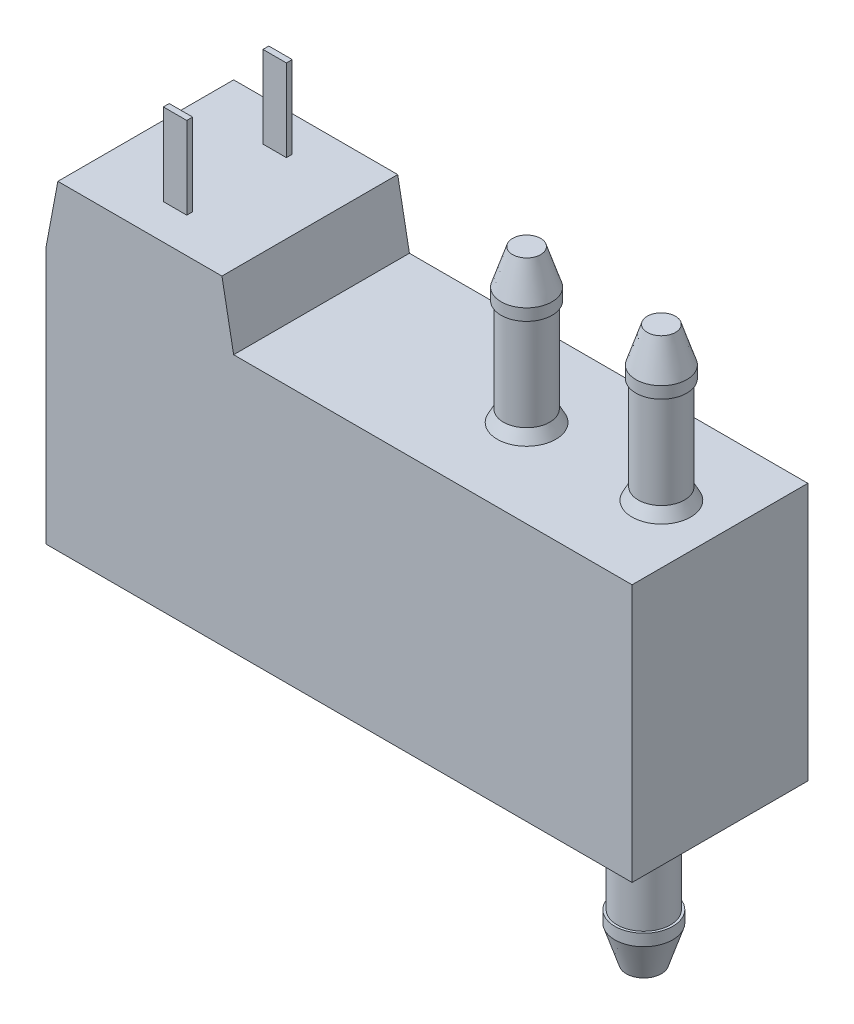
SolidWorks part; units mm, degrees
ref_plane "Front Plane" through (0, 0, 0) normal (0, 0, 1) x (1, 0, 0)
ref_plane "Top Plane" through (0, 0, 0) normal (0, 1, 0) x (1, 0, 0)
ref_plane "Right Plane" through (0, 0, 0) normal (1, 0, 0) x (0, 0, -1)
sketch "Sketch1" plane through (0, 0, 0) normal (0, 0, 1) x (1, 0, 0)
  line L1 (-25, -11) -> (25, -11)
  line L2 (-25, -11) -> (-25, 11)
  line L3 (-25, 11) -> (25, 11)
  line L4 (25, -11) -> (25, 11)
  line L5 (-25, -11) -> (25, 11) construction
  line L6 (-25, 11) -> (25, -11) construction
  point P0 (0, 0)
  dimension "D1" = 22
  dimension "D2" = 50
extrude "Boss-Extrude1" add sketch "Sketch1" along normal mid plane 15
sketch "Sketch3" plane through (0, 0, 0) normal (0, 0, 1) x (1, 0, 0)
  line L0 (-25, 11) -> (-24, 16.316)
  line L1 (-24, 16.316) -> (-10, 16.316)
  line L2 (-10, 16.316) -> (-9, 11)
  line L3 (25, 11) -> (-25, 11) construction
  line L4 (-9, 11) -> (-25, 11)
  point P4 (-17, 16.316)
  point P8 (-17, 11)
  dimension "D1" = 16
  dimension "D2" = 14
extrude "Boss-Extrude3" add sketch "Sketch3" along normal up to surface and the other way up to surface up to face at (0, 0, 7.5) other way up to face at (0, 0, -7.5)
sketch "Sketch4" plane through (0, 11, 0) normal (0, 1, 0) x (1, 0, 0)
  line L0 (25, 0) -> (-9, 0) construction
  line L1 (25, -7.5) -> (25, 7.5) construction
  line L2 (-9, -7.5) -> (-9, 7.5) construction
  point P6 (8.5, 0)
  point P7 (20, 0)
  dimension "D1" = 16.5
  dimension "D2" = 5
ref_axis "Axis1" through (8.5, 11, 0) along (0, 1, 0)
ref_axis "Axis2" through (20, 11, 0) along (0, 1, 0)
sketch "Sketch5" plane through (0, 0, 0) normal (0, 0, 1) x (1, 0, 0)
  line L0 (8.5, 11) -> (11, 11)
  line L1 (25, 11) -> (-9, 11) construction
  line L2 (11, 11) -> (10.4748, 12)
  line L3 (10.4748, 12) -> (10.4748, 20)
  line L4 (10.4748, 20) -> (10.6748, 20)
  line L5 (10.6748, 20) -> (10.6748, 21)
  line L6 (10.6748, 21) -> (9.7, 24)
  line L7 (9.7, 24) -> (8.5, 24)
  line L8 (8.5, 11) -> (8.5, 23.2634) construction
  line L9 (8.5, 24) -> (8.5, 11)
  dimension "D1" = 13
  dimension "D2" = 18
  dimension "D3" = 1
  dimension "D4" = 3
  dimension "D5" = 1
  dimension "D6" = 2.5
  dimension "D7" = 1.2
  dimension "D8" = 0.2
revolve "Revolve1" add sketch "Sketch5" angle 360 about L9
sketch "Sketch6" plane through (0, 0, 0) normal (0, 0, 1) x (1, 0, 0)
  line L0 (20, 11) -> (22.5, 11)
  line L1 (22.5, 11) -> (21.9748, 12)
  line L2 (21.9748, 12) -> (21.9748, 20)
  line L3 (21.9748, 20) -> (22.1748, 20)
  line L4 (22.1748, 20) -> (22.1748, 21)
  line L5 (22.1748, 21) -> (21.2, 24)
  line L6 (21.2, 24) -> (20, 24)
  line L7 (20, 24) -> (20, 11)
revolve "Revolve2" add sketch "Sketch6" angle 360 about L7
sketch "Sketch7" plane through (0, -11, 0) normal (0, -1, 0) x (1, 0, 0)
  line L0 (25, 0) -> (-9, 0) construction
  line L1 (25, 7.5) -> (25, -7.5) construction
  point P0 (18.5, 0)
  dimension "D1" = 6.5
ref_axis "Axis3" through (18.5, -11, 0) along (0, -1, 0)
sketch "Sketch8" plane through (0, 0, 0) normal (0, 0, 1) x (1, 0, 0)
  line L0 (18.5, -11) -> (18.5, -24)
  line L1 (18.5, -11) -> (18.5, -28.2265) construction
  line L2 (18.5, -24) -> (17, -24)
  line L3 (17, -24) -> (16.0252, -21)
  line L4 (16.0252, -21) -> (16.0252, -20)
  line L5 (16.0252, -20) -> (16.2252, -20)
  line L6 (16.2252, -20) -> (16.2252, -12)
  line L7 (16.2252, -12) -> (16, -11)
  line L8 (16, -11) -> (18.5, -11)
  line L9 (-25, -11) -> (25, -11) construction
  dimension "D1" = 1.5
  dimension "D2" = 13
  dimension "D3" = 18
  dimension "D4" = 0.2
  dimension "D5" = 1
  dimension "D6" = 3
  dimension "D7" = 2.5
  dimension "D8" = 1
revolve "Revolve3" add sketch "Sketch8" angle 360 about L0
sketch "Sketch9" plane through (0, 16.316, 0) normal (0, 1, 0) x (1, 0, 0)
  line L0 (-24, 0) -> (-10, 0) construction
  line L1 (-24, -7.5) -> (-24, 7.5) construction
  line L2 (-18, 4.5) -> (-16, 4.5)
  line L3 (-18, 4.5) -> (-18, 4)
  line L4 (-18, 4) -> (-16, 4)
  line L5 (-16, 4.5) -> (-16, 4)
  line L6 (-18, 4.5) -> (-16, 4) construction
  line L7 (-18, 4) -> (-16, 4.5) construction
  line L8 (-10, -7.5) -> (-10, 7.5) construction
  point P3 (-17, 4.25)
  point P12 (-17, 0)
  point P13 (-17, 4)
  dimension "D1" = 0.5
  dimension "D2" = 2
  dimension "D3" = 4
extrude "Boss-Extrude4" add sketch "Sketch9" along normal blind 7
mirror "Mirror1" about plane through (0, 0, 0) normal (0, 0, 1) of "Boss-Extrude4"
